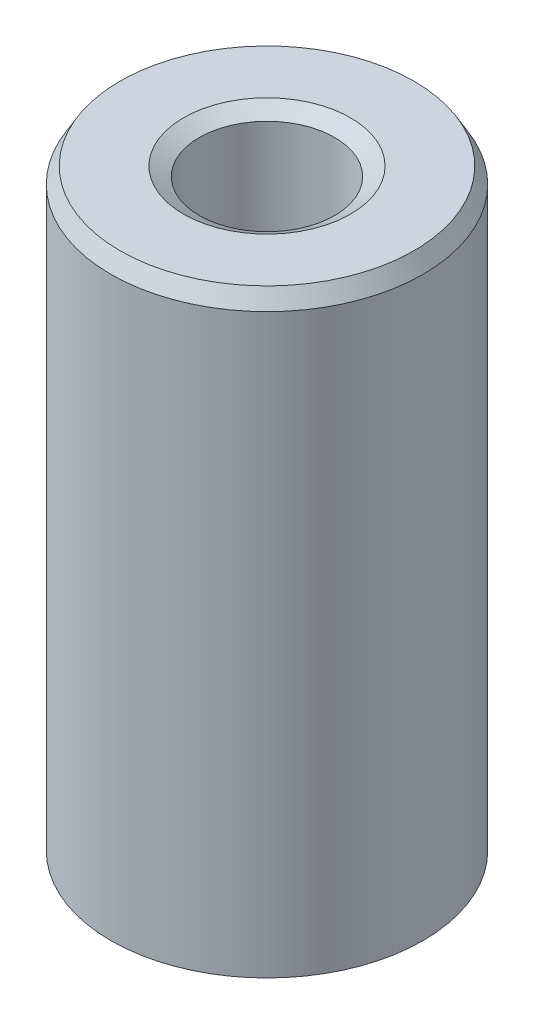
SolidWorks part; units mm, degrees
ref_plane "Front Plane" through (0, 0, 0) normal (0, 0, 1) x (1, 0, 0)
ref_plane "Top Plane" through (0, 0, 0) normal (0, 1, 0) x (1, 0, 0)
ref_plane "Right Plane" through (0, 0, 0) normal (1, 0, 0) x (0, 0, -1)
sketch "Sketch1" plane through (0, 0, 0) normal (0, 1, 0) x (1, 0, 0)
  circle A0 centre (0, 0) radius 17.5
  dimension "SLEEVE_OD" = 35
extrude "Boss-Extrude1" add sketch "Sketch1" along normal blind 67.4985
sketch "Sketch2" plane through (0, 0, 0) normal (0, 1, 0) x (1, 0, 0)
  circle A0 centre (0, 0) radius 7.5872
  dimension "BORE_D" = 15.1744
extrude "Cut-Extrude1" cut sketch "Sketch2" along normal through all
chamfer "Chamfer1" distance 1.7758 angle 30 4 edges at (0, 67.4985, 7.5872) (0, 0, 7.5872) (0, 0, 17.5) (0, 67.4985, 17.5) first distance on face at (0, 67.4985, 7.5872) first distance on face at (0, 0, 7.5872) first distance on face at (0, 67.4985, 17.5)
